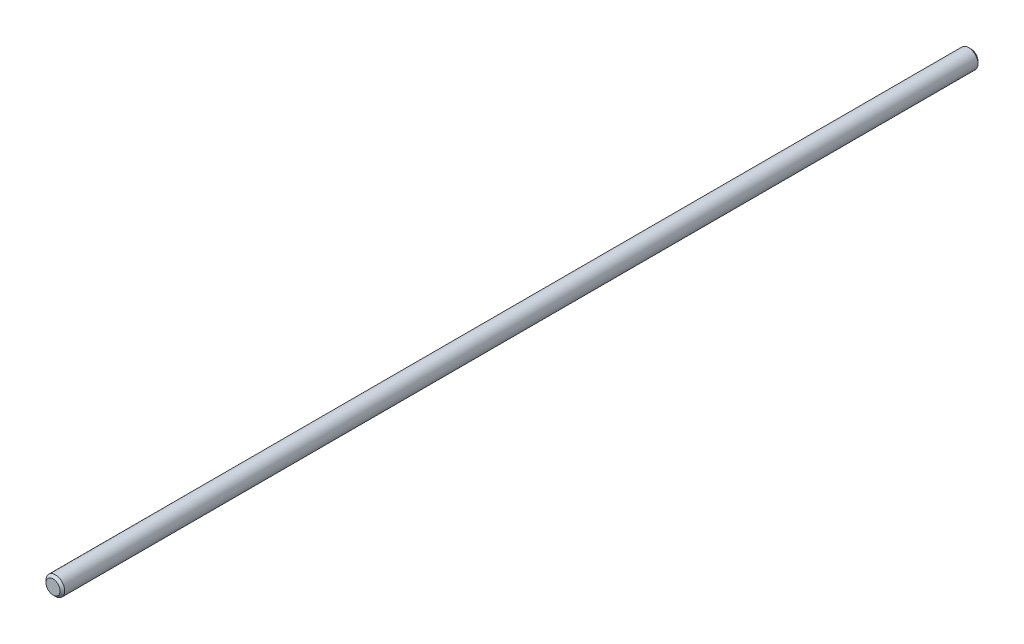
SolidWorks part; units mm, degrees
ref_plane "Front Plane" through (0, 0, 0) normal (0, 0, 1) x (1, 0, 0)
ref_plane "Top Plane" through (0, 0, 0) normal (0, 1, 0) x (1, 0, 0)
ref_plane "Right Plane" through (0, 0, 0) normal (1, 0, 0) x (0, 0, -1)
sketch "Sketch1" plane through (0, 0, 0) normal (0, 0, 1) x (1, 0, 0)
  circle A0 centre (0, 0) radius 4
  dimension "D1" = 8
extrude "Boss-Extrude1" add sketch "Sketch1" along normal blind 392
chamfer "Chamfer1" distance 1 angle 45 2 edges at (4, 0, 392) (4, 0, 0)
